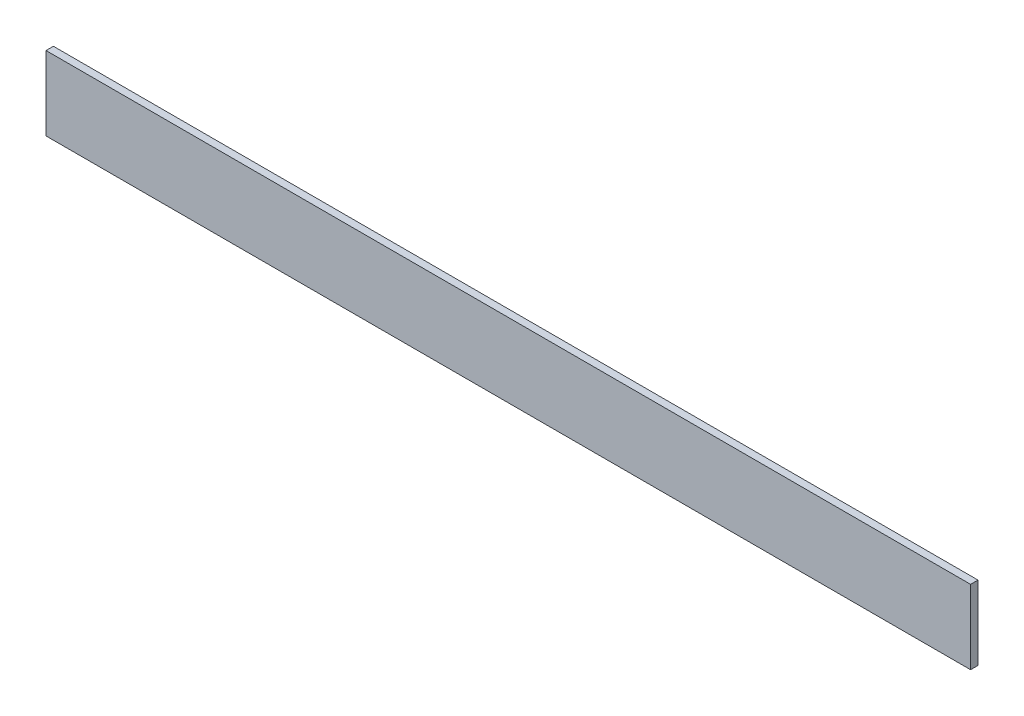
SolidWorks part; units mm, degrees
ref_plane "Ön Düzlem" through (0, 0, 0) normal (0, 0, 1) x (1, 0, 0)
ref_plane "Üst Düzlem" through (0, 0, 0) normal (0, 1, 0) x (1, 0, 0)
ref_plane "Sağ Düzlem" through (0, 0, 0) normal (1, 0, 0) x (0, 0, -1)
sketch "Çizim1" plane through (0, 0, 0) normal (0, 0, 1) x (1, 0, 0)
  line L1 (0, 0) -> (1000, 0)
  line L2 (0, 0) -> (0, -80)
  line L3 (0, -80) -> (1000, -80)
  line L4 (1000, 0) -> (1000, -80)
  dimension "D1" = 1000
  dimension "D2" = 80
base flange "Taban-Flanş1" sketch "Çizim1" thickness 8 reverse thickness direction no parameters "D1"=6
sketch "Büküm-Çizgileri1" [suppressed] plane through (0, 0, 0) normal (0, 1, 0) x (1, 0, 0)
sketch "Sınırlandırma-Kutusu1" [suppressed] plane through (0, 0, 0) normal (0, 1, 0) x (1, 0, 0)
sheet metal parameters "Sac-Levha1" thickness 8 parameters "D1"=6
flat pattern "Düz-Çoğaltma1" [suppressed]
sketch "Büküm-Çizgileri2" plane through (0, 0, 0) normal (0, 1, 0) x (1, 0, 0)
sketch3d "Sınırlandırma-Kutusu2" [suppressed]
  line L0 (0, -80, 0) -> (1000, -80, 0) construction
  line L1 (0, 0, 0) -> (1000, 0, 0) construction
  line L2 (0, -80, 0) -> (0, 0, 0) construction
  line L3 (1000, -80, 0) -> (1000, 0, 0) construction
